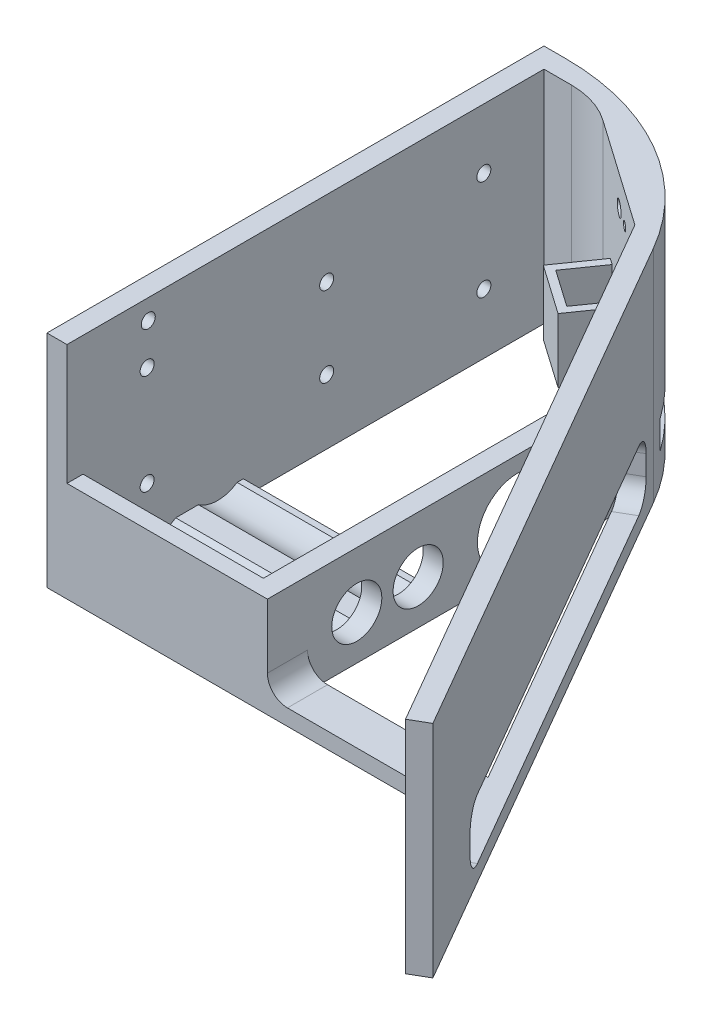
SolidWorks part; units mm, degrees
ref_plane "Front" through (0, 0, 0) normal (0, 0, 1) x (1, 0, 0)
ref_plane "Top" through (0, 0, 0) normal (0, 1, 0) x (1, 0, 0)
ref_plane "Right" through (0, 0, 0) normal (1, 0, 0) x (0, 0, -1)
sketch "Sketch3" plane through (0, 0, 0) normal (0, 1, 0) x (1, 0, 0)
  line L0 (128.1699, -162.7147) -> (55, -35.9808)
  line L1 (0, 0) -> (40, 0)
  line L2 (0, 0) -> (0, -124)
  line L3 (0, -124) -> (5, -124)
  line L4 (5, -5) -> (5, -124)
  line L5 (40, 0) -> (132.5, -160.2147)
  line L6 (132.5, -160.2147) -> (128.1699, -162.7147)
  line L7 (5, -5) -> (18.123, -5)
  line L10 (50, -27.3205) -> (50, -124)
  line L11 (50, -124) -> (55, -124)
  line L12 (55, -35.9808) -> (55, -124)
  line L13 (18.123, -5) -> (50, -27.3205)
  dimension "D1" = 5
  dimension "D2" = 5
  dimension "D3" = 5
  dimension "D4" = 120
  dimension "D5" = 124
  dimension "D6" = 185
  dimension "D7" = 40
  dimension "D8" = 5
  dimension "D9" = 45
  dimension "D10" = 145
extrude "Boss-Extrude3" add sketch "Sketch3" along normal blind 55 contours L2 L3 L4 L7 L13 L10 L11 L12 L0 L6 L5 L1
fillet "Fillet1" radius 60 1 edges at (40, 27.5, 0)
sketch "Sketch4" plane through (3.6131, 0, -5.16) normal (-0.5736, 0, 0.8192) x (0.8192, 0, 0.5736)
  line L1 (31.628, 30.3662) -> (46.628, 30.3662)
  line L2 (31.628, 30.3662) -> (31.628, 14.3662)
  line L3 (31.628, 14.3662) -> (46.628, 14.3662)
  line L4 (46.628, 30.3662) -> (46.628, 14.3662)
  line L5 (56.628, 55) -> (56.628, 0) construction
  dimension "D1" = 15
  dimension "D2" = 16
  dimension "D3" = 10
extrude "Boss-Extrude4" add sketch "Sketch4" along normal blind 12
sketch "Sketch5" plane through (3.6131, 0, -5.16) normal (-0.5736, 0, 0.8192) x (0.8192, 0, 0.5736)
  line L1 (19.128, 14.3662) -> (59.128, 14.3662)
  line L2 (19.128, 14.3662) -> (19.128, 7.3662)
  line L3 (19.128, 7.3662) -> (59.128, 7.3662)
  line L4 (59.128, 14.3662) -> (59.128, 7.3662)
  line L5 (39.128, 14.3662) -> (39.128, -8.9782) construction
  line L6 (31.628, 14.3662) -> (46.628, 14.3662) construction
  dimension "D1" = 40
  dimension "D2" = 7
extrude "Cut-Extrude1" cut sketch "Sketch5" against normal blind 14 and the other way blind 20
sketch "Sketch6" plane through (0, 30.3662, 0) normal (0, 1, 0) x (1, 0, 0)
  line L0 (31.0776, -14.0709) -> (25.2845, -22.3443)
  line L1 (25.2845, -22.3443) -> (34.459, -28.7684)
  line L2 (34.459, -28.7684) -> (40.2521, -20.4949)
  line L3 (40.2521, -20.4949) -> (31.0776, -14.0709)
  line L4 (34.9256, -31.4146) -> (41.8085, -21.5847) construction
  line L5 (22.6383, -22.8109) -> (29.5212, -12.9811) construction
  line L6 (34.9256, -31.4146) -> (22.6383, -22.8109) construction
  line L7 (41.8085, -21.5847) -> (29.5212, -12.9811) construction
  dimension "D1" = 1.9
  dimension "D2" = 1.9
  dimension "D3" = 1.9
extrude "Cut-Extrude2" cut sketch "Sketch6" against normal offset from surface (14 mm away) 2
sketch "Sketch7" plane through (0, 16.3662, 0) normal (0, 1, 0) x (1, 0, 0)
  line L0 (31.0776, -14.0709) -> (34.459, -28.7684) construction
  line L1 (34.459, -28.7684) -> (25.2845, -22.3443) construction
  circle A0 centre (32.7683, -21.4196) radius 2
  dimension "D1" = 4
extrude "Cut-Extrude3" cut sketch "Sketch7" against normal blind 2
sketch "Sketch8" plane through (0, 55, 0) normal (0, 1, 0) x (1, 0, 0)
  line L0 (55, -35.9808) -> (50, -27.3205)
  line L1 (50, -27.3205) -> (50, -124)
  line L2 (50, -124) -> (55, -124)
  line L3 (55, -124) -> (55, -35.9808)
extrude "Cut-Extrude4" cut sketch "Sketch8" against normal blind 30
sketch "Sketch9" plane through (50, 0, 0) normal (-1, 0, 0) x (0, 0, 1)
  line L0 (27.3205, 0) -> (124, 0) construction
  circle A0 centre (61.5987, 11) radius 10
  circle A1 centre (86.3851, 11) radius 6.25
  circle A2 centre (101.7, 11) radius 6.25
  dimension "D1" = 12.5
  dimension "D2" = 12.5
  dimension "D3" = 20
  dimension "D4" = 11
extrude "Cut-Extrude5" cut sketch "Sketch9" against normal up to surface (5 mm away) up to face at (55, 12.5, 79.9904)
sketch "Sketch10" plane through (30, 0, -17.3205) normal (0.866, 0, -0.5) x (-0.5, 0, -0.866)
  line L0 (-54.641, 0) -> (-205, 0) construction
  line L1 (-179.641, 4) -> (-59.641, 4)
  line L2 (-179.641, 4) -> (-179.641, 19)
  line L3 (-179.641, 19) -> (-59.641, 19)
  line L4 (-59.641, 4) -> (-59.641, 19)
  line L5 (-54.641, 0) -> (-54.641, 55) construction
  dimension "D1" = 15
  dimension "D2" = 4
  dimension "D3" = 120
  dimension "D4" = 5
extrude "Cut-Extrude6" cut sketch "Sketch10" against normal up to surface (5 mm away) up to face at (77.7233, 26.6667, 75.3387)
sketch "Sketch11" plane through (50, 0, 0) normal (-1, 0, 0) x (0, 0, 1)
  line L0 (27.3205, 0) -> (124, 0) construction
  line L1 (124, 25) -> (120, 25)
  line L2 (124, 25) -> (124, 0)
  line L3 (124, 0) -> (120, 0)
  line L4 (120, 25) -> (120, 0)
  dimension "D1" = 4
extrude "Boss-Extrude5" add sketch "Sketch11" along normal up to surface (45 mm away) up to face at (5, 27.5, 64.5)
fillet "Fillet3" radius 20 1 edges at (18.123, 27.5, 5)
sketch "Sketch12" plane through (55, 0, 0) normal (1, 0, 0) x (0, 0, -1)
  line L1 (-124, 0) -> (-114, 0)
  line L2 (-124, 0) -> (-124, 4)
  line L3 (-124, 4) -> (-114, 4)
  line L4 (-114, 0) -> (-114, 4)
  dimension "D1" = 10
  dimension "D2" = 4
extrude "Boss-Extrude6" add sketch "Sketch12" along normal up to surface (50.8179 mm away) up to face at (85.4904, 11.5, 88.7917)
sketch "Sketch13" plane through (50, 0, 0) normal (-1, 0, 0) x (0, 0, 1)
  line L1 (80, 0) -> (120, 0)
  line L2 (80, 0) -> (80, 4)
  line L3 (80, 4) -> (120, 4)
  line L4 (120, 0) -> (120, 4)
  line L5 (120, 25) -> (120, 0) construction
  dimension "D1" = 4
  dimension "D2" = 40
extrude "Boss-Extrude7" add sketch "Sketch13" along normal up to surface (45 mm away) up to face at (5, 26.6667, 83)
fillet "Fillet4" radius 5 4 edges at (57.6554, 4, 35.5801) (117.6554, 4, 139.5032) (117.6554, 19, 139.5032) (57.6554, 19, 35.5801)
fillet "Fillet5" radius 5 1 edges at (55, 4, 119)
sketch "Sketch14" plane through (50, 0, 0) normal (-1, 0, 0) x (0, 0, 1)
  arc A0 (94.0426, 14.6896) -> (94.0426, 7.3104) centre (86.3851, 11) ccw
  arc A1 (94.0426, 7.3104) -> (94.0426, 14.6896) centre (101.7, 11) ccw
  circle A2 centre (101.7, 11) radius 6.25 construction
  circle A3 centre (86.3851, 11) radius 6.25 construction
  dimension "D1" = 17
  dimension "D2" = 17
extrude "Cut-Extrude7" cut sketch "Sketch14" along normal up to surface (45 mm away) up to face at (5, 21, 82.25)
sketch "Sketch15" plane through (0, 0, 0) normal (-1, 0, 0) x (0, 0, 1)
  line L0 (0, 55) -> (124, 55) construction
  line L1 (0, 55) -> (0, 0) construction
  line L2 (0, 0) -> (124, 0) construction
  line L3 (124, 55) -> (124, 0) construction
  circle A0 centre (104, 40) radius 1.75
  circle A1 centre (104, 15) radius 1.75
  circle A2 centre (20, 15) radius 1.75
  circle A3 centre (20, 40) radius 1.75
  dimension "D1" = 3.5
  dimension "D2" = 15
  dimension "D3" = 20
  dimension "D4" = 15
  dimension "D5" = 20
sketch "Sketch16" plane through (0, 0, 0) normal (-1, 0, 0) x (0, 0, 1)
  circle A0 centre (59.2085, 36.1358) radius 1.75
  circle A1 centre (59.2085, 16.1358) radius 1.75
  circle A2 centre (103.7183, 50.0137) radius 1.75
  dimension "D1" = 3.5
  dimension "D2" = 3.5
  dimension "D3" = 3.5
extrude "Cut-Extrude8" cut sketch "Sketch16" against normal up to surface (5 mm away) up to face at (5, 15.0833, 86.1809)
extrude "Cut-Extrude9" cut sketch "Sketch15" against normal blind 5
sketch "Sketch17" plane through (30, 0, -17.3205) normal (0.866, 0, -0.5) x (-0.5, 0, -0.866)
  line L0 (-49.2023, 7.3662) -> (-49.2023, 14.3662) construction
  line L1 (-2.6795, 55) -> (-54.641, 55) construction
  circle A0 centre (-34.2023, 47.5) radius 1.75
  circle A1 centre (-39.2023, 47.5) radius 1
  dimension "D1" = 2
  dimension "D2" = 3.5
  dimension "D3" = 5
  dimension "D4" = 10
  dimension "D5" = 7.5
extrude "Cut-Extrude10" cut sketch "Sketch17" against normal up to next
